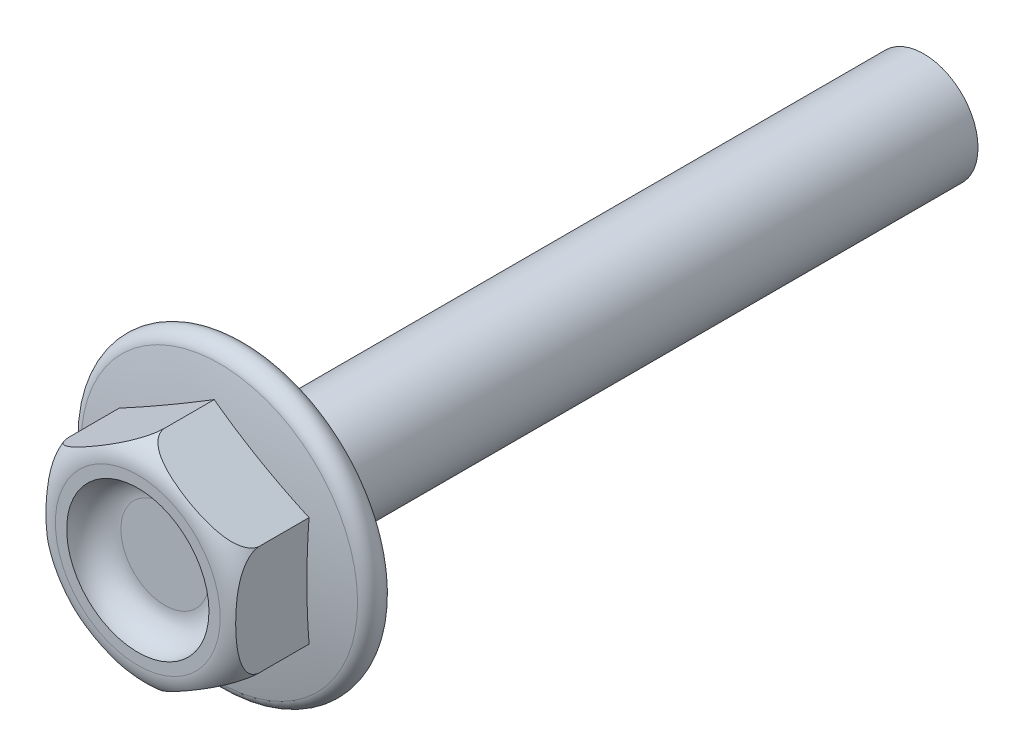
SolidWorks part; units mm, degrees
extrude "Shank" add sketch "Shank Sketch" against normal blind 25
sketch "Shank Sketch" plane through (0, 0, 0) normal (0, 0, 1) x (1, 0, 0)
  line L0 (50, 0) -> (-50, 0) construction
  line L1 (0, -50) -> (0, 50) construction
  circle A0 centre (0, 0) radius 2
  dimension "Shank diameter" = 4
extrude "Head" add sketch "Head Sketch" along normal blind 4
sketch "Head Sketch" plane through (0, 0, 0) normal (0, 0, 1) x (1, 0, 0)
  line L0 (0, 4.0415) -> (3.5, 2.0207)
  line L1 (3.5, 2.0207) -> (3.5, -2.0207)
  line L2 (3.5, -2.0207) -> (0, -4.0415)
  line L3 (0, -4.0415) -> (-3.5, -2.0207)
  line L4 (-3.5, -2.0207) -> (-3.5, 2.0207)
  line L5 (-3.5, 2.0207) -> (0, 4.0415)
  line L6 (3.5, 2.0207) -> (-3.5, -2.0207) construction
  line L7 (0, 4.0415) -> (0, -4.0415) construction
  line L8 (-3.5, 2.0207) -> (3.5, -2.0207) construction
  point P0 (0, 0)
  dimension "D1" = 60
  dimension "D2" = 60
  dimension "Width across flats" = 7
material "Plain Carbon Steel"
ref_plane "Plane1" through (0, 0, 0) normal (0, 0, 1) x (1, 0, 0)
ref_plane "Plane2" through (0, 0, 0) normal (0, 1, 0) x (-1, 0, 0)
ref_plane "Plane3" through (0, 0, 0) normal (1, 0, 0) x (0, 0, -1)
sketch "Sketch3" plane through (0, 0, 0) normal (0, 1, 0) x (-1, 0, 0)
  line L0 (0, 0) -> (0, 3) construction
  line L1 (0, -25) -> (0, 0) construction
  line L4 (-5, 0) -> (0, 0)
  line L5 (0, 0) -> (0, 1.5)
  arc A0 (0, 1.5) -> (-5.099, 0.9901) centre (0, -24.25) ccw
  arc A1 (-5, 0) -> (-5.099, 0.9901) centre (-5, 0.5) cw
  dimension "D1" = 0.5
  dimension "D2" = 10
  dimension "D3" = 1.5
revolve "Flange" add sketch "Sketch3" angle 360 about L0
sketch "Sketch5" plane through (0, 0, 0) normal (1, 0, 0) x (0, 0, -1)
  line L0 (-4, -3.0415) -> (-4, -4.0415)
  line L1 (-4, -4.0415) -> (-3, -4.0415)
  line L2 (-4, -4.0415) -> (-1.1809, -4.0415) construction
  line L3 (-4, -4.0415) -> (-4, -2.0207) construction
  line L5 (-15.0856, 0) -> (-8.1394, 0) construction
  line L6 (50, 0) -> (-50, 0) construction
  arc A0 (-4, -3.0415) -> (-3, -4.0415) centre (-3, -3.0415) ccw
  dimension "D1" = 1
revolve "Head Trim" cut sketch "Sketch5" angle 360 about L5
sketch "Sketch6" plane through (0, 0, 4) normal (0, 0, 1) x (1, 0, 0)
  circle A3 centre (0, 0) radius 2.625
  dimension "D1" = 5.25
extrude "Head Cut" cut sketch "Sketch6" against normal blind 1
fillet "Fillet1" radius 1 1 edges at (2.625, 0, 3)
equation "\"D1@Sketch6\" = \"Width across flats@Head Sketch\"*3/4"
